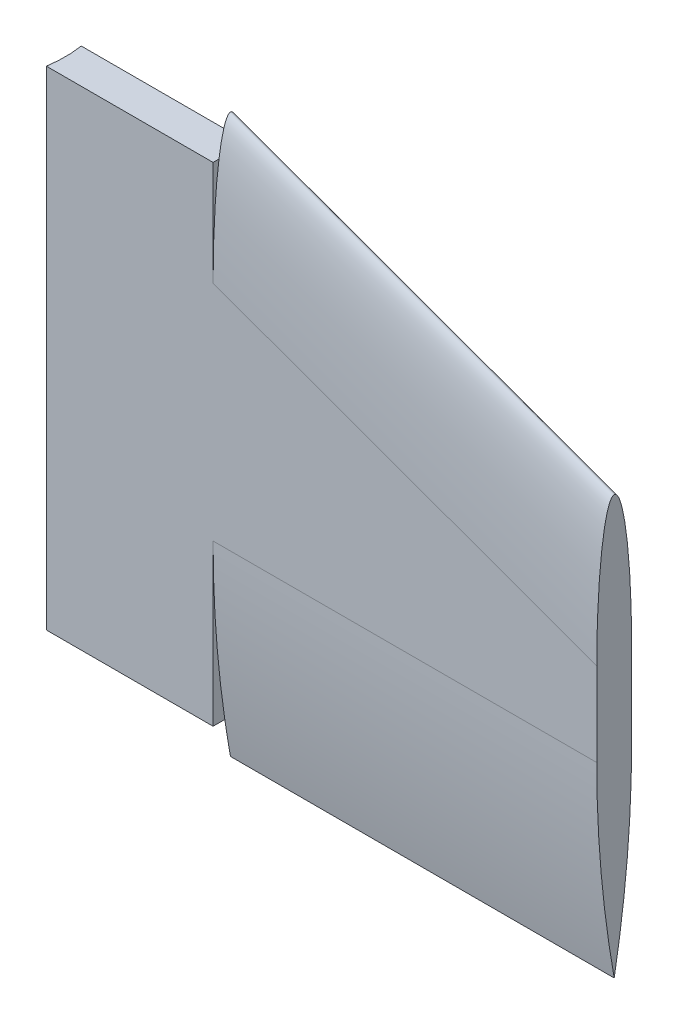
SolidWorks part; units mm, degrees
other "Markup1"
sketch "Sketch2" plane through (0, -5, 5) normal (-0.9994, -0.0223, 0.0275) x (0.021, 0.2509, 0.9678)
ref_plane "Front Plane" through (0, 0, 0) normal (0, 0, 1) x (1, 0, 0)
ref_plane "Top Plane" through (0, 0, 0) normal (0, 1, 0) x (1, 0, 0)
ref_plane "Right Plane" through (0, 0, 0) normal (1, 0, 0) x (0, 0, -1)
sketch "Sketch1" plane through (0, 0, 0) normal (0, 0, 1) x (1, 0, 0)
  line L0 (0, 0) -> (0, 70)
  line L1 (0, 70) -> (25, 70)
  line L5 (80, -5) -> (25, -5)
  line L6 (25, -5) -> (25, 0)
  line L7 (25, 0) -> (0, 0)
  line L8 (25, 70) -> (25, 75)
  line L9 (25, 75) -> (80, 55)
  line L10 (80, 55) -> (80, -5)
  line L11 (25, 75) -> (25, -5) construction
  point P3 (25, 35)
  point P10 (0, 35)
  dimension "D1" = 80
  dimension "D2" = 60
  dimension "D3" = 55
  dimension "D4" = 25
  dimension "D5" = 70
extrude "Boss-Extrude1" add sketch "Sketch1" along normal blind 5
sketch "Sketch4" plane through (80, 0, 0) normal (1, 0, 0) x (0, 0, -1)
  line L0 (-5, 55) -> (0, 55) construction
  line L1 (-5, 35) -> (0, 35) construction
  line L2 (-5, -5) -> (-5, 55) construction
  line L3 (0, -5) -> (0, 55) construction
  line L4 (-5, 35) -> (-5, 55)
  line L5 (-5, 55) -> (0, 55)
  line L6 (0, 55) -> (0, 35)
  ellipse E0 centre (-2.5, 35) end of major axis (-2.5, 55) minor radius 2.5 (0, 35) -> (-5, 35) ccw
  line M3 (0, -5) -> (0, 55)
  line M4 (0, 55) -> (-5, 55)
  line M5 (-5, 55) -> (-5, -5)
  dimension "D1" = 20
extrude "Cut-Extrude2" cut sketch "Sketch4" along direction (-0.9398, 0.3417, 0) on the side against the normal up to surface (55 mm away) contours E0 L5 M5 | E0 M3 M4
sketch "Sketch5" plane through (80, 0, 0) normal (1, 0, 0) x (0, 0, -1)
  line L0 (-5, -5) -> (0, -5) construction
  line L1 (0, -5) -> (0, 35) construction
  line L2 (-158.05, 23) -> (0, 23) construction
  line L3 (-2.5, -5) -> (-2.5, 55) construction
  line L4 (-5, 23) -> (-5, -5)
  line L5 (-5, -5) -> (0, -5)
  line L6 (0, -5) -> (0, 23)
  circle A0 centre (-158.05, 23) radius 158.05 construction
  arc A1 (0, 23) -> (-2.5, -5) centre (-158.05, 23) cw
  arc A2 (-5, 23) -> (-2.5, -5) centre (153.05, 23) ccw
  ellipse E0 centre (-2.5, 35) end of major axis (-2.5, 55) minor radius 2.5 (0, 35) -> (-5, 35) ccw construction
  point P0 (-2.5, -5)
  line M4 (0, -5) -> (0, 35)
  line M6 (-5, 35) -> (-5, -5)
  line M7 (-5, -5) -> (0, -5)
  dimension "D2" = 316.1
  dimension "D1" = 28
extrude "Cut-Extrude3" cut sketch "Sketch5" against normal up to surface (55 mm away) contours A2 M6 M7 | A1 L5 M4 up to face at (25, -2.5, 2.5)
sketch "Sketch6" plane through (0, 70, 0) normal (0, 1, 0) x (1, 0, 0)
  line L0 (25, -0.8464) -> (25, -4.1536) construction
  line L1 (25, -2.5) -> (-26.1039, -2.5) construction
  line L3 (0, -5) -> (0, 0) construction
  circle A0 centre (-14.6, -2.5) radius 39.6 construction
  circle A1 centre (-14.6, -2.5) radius 15.9
  point P9 (0, -2.5)
  dimension "D1" = 79.2
  dimension "D2" = 31.8
extrude "Cut-Extrude4" cut sketch "Sketch6" against normal through all
